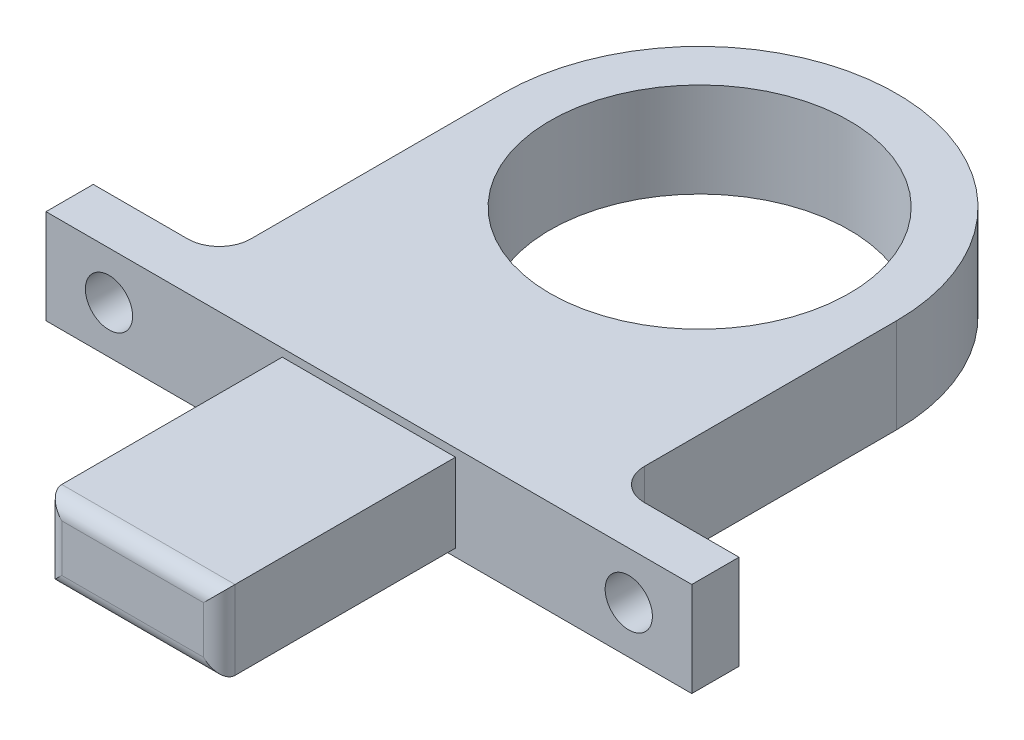
SolidWorks part; units mm, degrees
ref_plane "Alzado" through (0, 0, 0) normal (0, 0, 1) x (1, 0, 0)
ref_plane "Planta" through (0, 0, 0) normal (0, 1, 0) x (1, 0, 0)
ref_plane "Vista lateral" through (0, 0, 0) normal (1, 0, 0) x (0, 0, -1)
sketch "Croquis1" plane through (0, 0, 0) normal (0, 1, 0) x (1, 0, 0)
  line L0 (-12.5, 0) -> (12.5, 0) construction
  line L1 (-12.5, 0) -> (-12.5, -16)
  line L2 (-12.5, -21) -> (12.5, -21)
  line L3 (12.5, -16) -> (12.5, 0)
  line L4 (-20.5, -18) -> (20.5, -18) construction
  line L6 (-20.5, -18) -> (-14.5, -18)
  line L7 (-20.5, -18) -> (-20.5, -21)
  line L8 (-20.5, -21) -> (-12.5, -21)
  line L9 (-12.5, -14) -> (-12.5, -21)
  line L10 (20.5, -18) -> (14.5, -18)
  line L11 (20.5, -18) -> (20.5, -21)
  line L12 (20.5, -21) -> (12.5, -21)
  line L13 (12.5, -14) -> (12.5, -21)
  line L14 (-5.5, -21) -> (5.5, -21)
  line L15 (-5.5, -21) -> (-5.5, -36)
  line L16 (-5.5, -36) -> (5.5, -36)
  line L17 (5.5, -21) -> (5.5, -36)
  circle A0 centre (0, 0) radius 12.5
  circle A1 centre (0, 0) radius 9.5
  arc A2 (14.5, -18) -> (12.5, -16) centre (14.5, -16) cw
  arc A3 (-14.5, -18) -> (-12.5, -16) centre (-14.5, -16) ccw
  dimension "D1" = 25
  dimension "D2" = 19
  dimension "D6" = 2
  dimension "D3" = 21
  dimension "D4" = 3
  dimension "D5" = 8
  dimension "D7" = 8
  dimension "D8" = 25
  dimension "D9" = 12.5
  dimension "D10" = 11
  dimension "D11" = 15
  dimension "D12" = 5.5
extrude "Saliente-Extruir1" add sketch "Croquis1" along normal blind 6 contours A3 L6 L7 L8 L2 L12 L11 L10 A2 L3 A0 L1 | A0 A1 | A3 L6 L7 L8 L9 | L10 A2 L13 L12 L11 | L15 L14 L17 L16 region at (0, 0, 15.0607) region at (0, 0, -12.1464) region at (-16.3773, 0, 19.4328) region at (16.3773, 0, 19.4328)
sketch "Croquis2" plane through (0, 0, 21) normal (0, 0, 1) x (1, 0, 0)
  line L0 (-20.5, 3) -> (20.5, 3) construction
  line L1 (-20.5, 6) -> (-20.5, 0) construction
  line L2 (20.5, 6) -> (20.5, 0) construction
  circle A0 centre (-16.5, 3) radius 1.5
  circle A1 centre (16.5, 3) radius 1.5
  dimension "D3" = 3
  dimension "D4" = 3
  dimension "D1" = 4
  dimension "D2" = 4
extrude "Cortar-Extruir1" cut sketch "Croquis2" against normal blind 6
sketch "Croquis3" plane through (0, 0, 18) normal (0, 0, -1) x (-1, 0, 0)
  circle A0 centre (-16.5, 3) radius 3
  circle A1 centre (16.5, 3) radius 3
  dimension "D1" = 6
  dimension "D2" = 6
extrude "Cortar-Extruir2" cut sketch "Croquis3" along normal blind 6
sketch "Croquis4" plane through (0, 0, 0) normal (0, -1, 0) x (1, 0, 0)
  line L1 (-5.5, 36) -> (5.5, 36)
  line L2 (-5.5, 36) -> (-5.5, 21)
  line L3 (-5.5, 21) -> (5.5, 21)
  line L4 (5.5, 36) -> (5.5, 21)
extrude "Cortar-Extruir3" cut sketch "Croquis4" against normal blind 0.5
sketch "Croquis5" plane through (0, 6, 0) normal (0, 1, 0) x (1, 0, 0)
  line L1 (-5.5, -21) -> (5.5, -21)
  line L2 (-5.5, -21) -> (-5.5, -36)
  line L3 (-5.5, -36) -> (5.5, -36)
  line L4 (5.5, -21) -> (5.5, -36)
extrude "Cortar-Extruir4" cut sketch "Croquis5" against normal blind 0.5
fillet "Redondeo1" radius 1 4 edges at (5.5, 3, 36) (0, 0.5, 36) (-5.5, 3, 36) (0, 5.5, 36)
